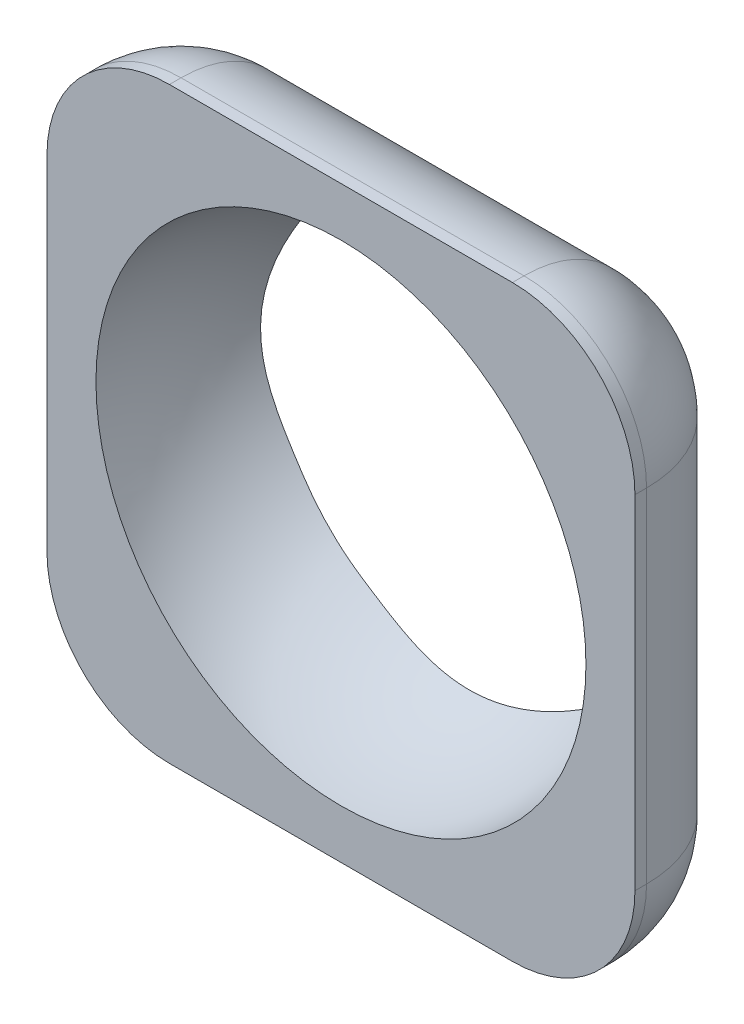
SolidWorks part; units mm, degrees
ref_plane "Front Plane" through (0, 0, 0) normal (0, 0, 1) x (1, 0, 0)
ref_plane "Top Plane" through (0, 0, 0) normal (0, 1, 0) x (1, 0, 0)
ref_plane "Right Plane" through (0, 0, 0) normal (1, 0, 0) x (0, 0, -1)
sketch "Sketch2" plane through (0, 0, 0) normal (0, 0, 1) x (1, 0, 0)
  line L1 (0, 0) -> (24, 0)
  line L2 (0, 0) -> (0, 24)
  line L3 (0, 24) -> (24, 24)
  line L4 (24, 0) -> (24, 24)
  dimension "D1" = 24
  dimension "D2" = 24
extrude "Boss-Extrude1" add sketch "Sketch2" along normal blind 10.5
sketch "Sketch4" plane through (0, 0, 10.5) normal (0, 0, 1) x (1, 0, 0)
  line L0 (12, 22) -> (12, 2)
  arc A0 (12, 22) -> (12, 2) centre (12, 12) ccw
revolve "Cut-Revolve1" cut sketch "Sketch4" angle 360 about L0
sketch "Sketch6" plane through (24, 0, 0) normal (1, 0, 0) x (0, 0, -1)
  line L0 (0, 24) -> (-3.0266, 24)
  line L1 (-10.5, 24) -> (0, 24) construction
  line L2 (0, 0) -> (-3.0266, 0)
  line L3 (-10.5, 0) -> (0, 0) construction
  line L5 (0, 0) -> (0, 24)
  line L6 (-3.0266, 24) -> (-5.0266, 24)
  line L7 (-5.0266, 24) -> (-5.0266, 0)
  line L8 (-5.0266, 0) -> (-3.0266, 0)
extrude "Cut-Extrude1" cut sketch "Sketch6" against normal through all
fillet "Fillet1" radius 5 8 edges at (12, 0, 5.0266) (24, 12, 5.0266) (12, 24, 5.0266) (0, 12, 5.0266) (0, 0, 7.7633) (0, 24, 7.7633) (24, 24, 7.7633) (24, 0, 7.7633)
